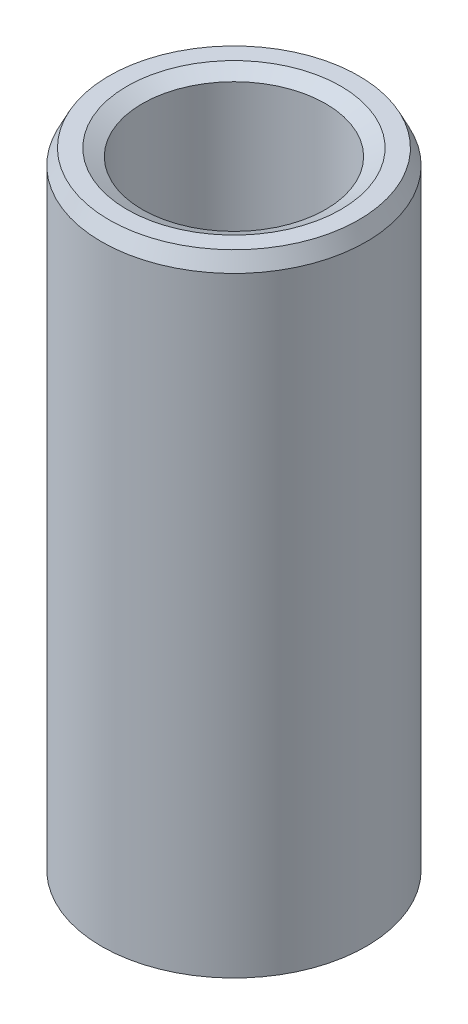
SolidWorks part; units mm, degrees
ref_plane "Front Plane" through (0, 0, 0) normal (0, 0, 1) x (1, 0, 0)
ref_plane "Top Plane" through (0, 0, 0) normal (0, 1, 0) x (1, 0, 0)
ref_plane "Right Plane" through (0, 0, 0) normal (1, 0, 0) x (0, 0, -1)
sketch "Sketch1" plane through (0, 0, 0) normal (0, 1, 0) x (1, 0, 0)
  circle A0 centre (0, 0) radius 10
  dimension "SLEEVE_OD" = 20
extrude "Boss-Extrude1" add sketch "Sketch1" along normal blind 47.815
sketch "Sketch2" plane through (0, 0, 0) normal (0, 1, 0) x (1, 0, 0)
  circle A0 centre (0, 0) radius 6.9279
  dimension "BORE_D" = 13.8558
extrude "Cut-Extrude1" cut sketch "Sketch2" along normal through all
chamfer "Chamfer1" distance 1.1474 angle 26.438 4 edges at (0, 47.815, 6.9279) (0, 0, 6.9279) (0, 0, 10) (0, 47.815, 10) first distance on face at (0, 47.815, 6.9279) first distance on face at (0, 0, 6.9279) first distance on face at (0, 47.815, 10)
